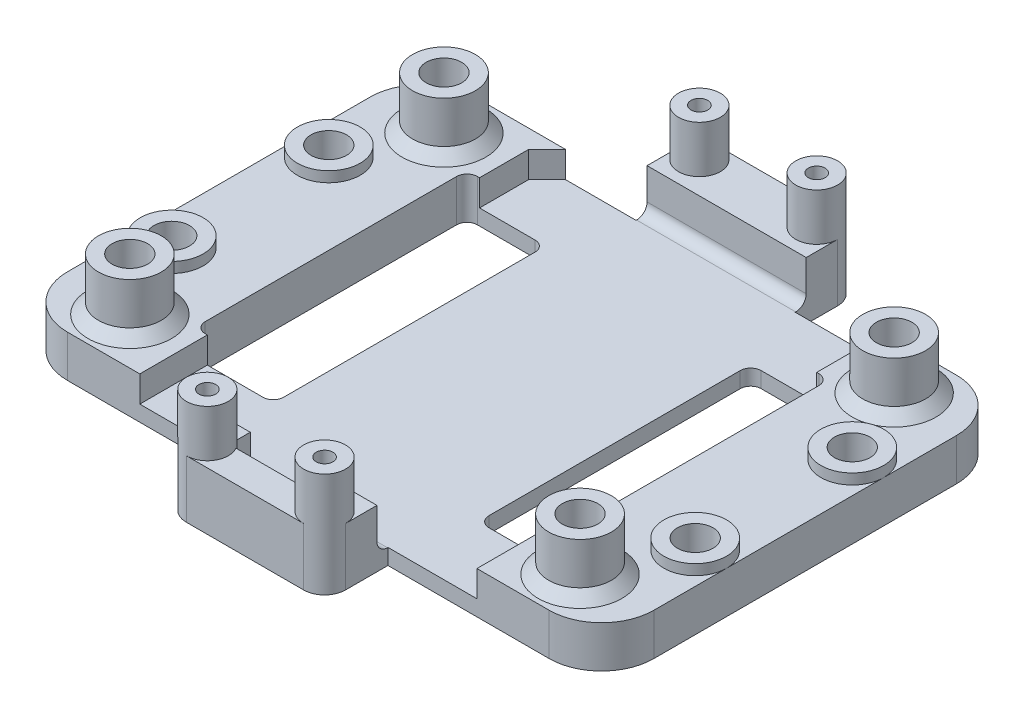
SolidWorks part; units mm, degrees
ref_plane "Front Plane" through (0, 0, 0) normal (0, 0, 1) x (1, 0, 0)
ref_plane "Top Plane" through (0, 0, 0) normal (0, 1, 0) x (1, 0, 0)
ref_plane "Right Plane" through (0, 0, 0) normal (1, 0, 0) x (0, 0, -1)
sketch "Sketch1" plane through (0, 0, 0) normal (0, 1, 0) x (1, 0, 0)
  line L0 (-15.6, 17.4701) -> (-13.6201, 19.45)
  line L1 (-13.6201, 19.45) -> (13.6201, 19.45)
  line L2 (-15.6, 17.4701) -> (-15.6, -19.45)
  line L3 (-15.6, -19.45) -> (15.6, -19.45)
  line L4 (15.6, 17.4701) -> (15.6, -19.45)
  line L5 (-14.7188, 18.3513) -> (15.6, -19.45) construction
  line L6 (-15.6, -19.45) -> (14.7188, 18.3513) construction
  line L7 (-13.6201, 19.45) -> (13.6201, 19.45)
  line L8 (13.6201, 19.45) -> (15.6, 17.4701)
  point P0 (0, 0)
  dimension "D1" = 31.2
  dimension "D2" = 38.9
  dimension "D3" = 45
  dimension "D4" = 2.8
  dimension "D5" = 2.8
  dimension "D6" = 19.45
  dimension "D7" = 15.6
sketch "Sketch2" plane through (0, 0, 0) normal (0, 1, 0) x (1, 0, 0)
  line L1 (-25, 7.5) -> (25, 7.5) construction
  line L2 (-25, 7.5) -> (-25, -7.5) construction
  line L3 (-25, -7.5) -> (25, -7.5) construction
  line L4 (25, 7.5) -> (25, -7.5) construction
  line L5 (-25, 7.5) -> (25, -7.5) construction
  line L6 (-25, -7.5) -> (25, 7.5) construction
  circle A0 centre (-25, 7.5) radius 1.7
  circle A1 centre (-25, -7.5) radius 1.7
  circle A2 centre (25, -7.5) radius 1.7
  circle A3 centre (25, 7.5) radius 1.7
  circle A4 centre (-25, 7.5) radius 3
  circle A5 centre (-25, -7.5) radius 3
  circle A6 centre (25, -7.5) radius 3
  circle A7 centre (25, 7.5) radius 3
  point P0 (0, 0)
  dimension "D3" = 3.4
  dimension "D4" = 6
  dimension "D1" = 50
  dimension "D2" = 15
extrude "Boss-Extrude1" add sketch "Sketch2" along normal blind 5
sketch "Sketch3" plane through (0, 0, 0) normal (0, 1, 0) x (1, 0, 0)
  line L0 (-13.6201, 19.45) -> (13.6201, 19.45) construction
  line L1 (-28, -19.45) -> (28, -19.45)
  line L2 (-28, -19.45) -> (-28, 19.45)
  line L3 (-28, 19.45) -> (28, 19.45)
  line L4 (28, -19.45) -> (28, 19.45)
  line L5 (-28, -19.45) -> (28, 19.45) construction
  line L6 (-28, 19.45) -> (28, -19.45) construction
  circle A0 centre (-25, 7.5) radius 3 construction
  circle A1 centre (-25, 7.5) radius 1.7 construction
  circle A2 centre (-25, 7.5) radius 1.7
  circle A3 centre (25, 7.5) radius 1.7 construction
  circle A4 centre (25, -7.5) radius 1.7 construction
  circle A5 centre (-25, -7.5) radius 1.7 construction
  circle A6 centre (25, 7.5) radius 1.7
  circle A7 centre (25, -7.5) radius 1.7
  circle A8 centre (-25, -7.5) radius 1.7
  point P0 (0, 0)
extrude "Boss-Extrude2" add sketch "Sketch3" along normal blind 4
fillet "Fillet1" radius 5 4 edges at (-28, 2, -19.45) (28, 2, -19.45) (28, 2, 19.45) (-28, 2, 19.45)
extrude "Cut-Extrude2" cut sketch "Sketch1" against normal blind 2.5 from surface contours L8 L1 L0 L2 L3 L4 region at (0, 0, 0.0609) starting at face at (0, 4, -0.75)
sketch "Sketch4" plane through (0, 4, 0) normal (0, 1, 0) x (1, 0, 0)
  line L41 (-16.1, -19.95) -> (16.1, -19.95)
  line L42 (13.8272, 19.95) -> (-13.8272, 19.95)
  line L43 (16.1, -19.95) -> (16.1, 17.6772)
  line L44 (16.1, 17.6772) -> (13.8272, 19.95)
  line L45 (-16.1, 17.6772) -> (-16.1, -19.95)
  line L46 (-13.8272, 19.95) -> (-16.1, 17.6772)
  line L47 (-16.1, -19.95) -> (16.1, -19.95)
  line L48 (13.8272, 19.95) -> (-13.8272, 19.95)
  line L49 (16.1, -19.95) -> (16.1, 17.6772)
  line L50 (16.1, 17.6772) -> (13.8272, 19.95)
  line L51 (-16.1, 17.6772) -> (-16.1, -19.95)
  line L52 (-13.8272, 19.95) -> (-16.1, 17.6772)
  dimension "D1" = 0.5
extrude "Cut-Extrude3" cut sketch "Sketch4" against normal up to surface (2.5 mm away) up to face at (0, 1.5, -5.8234)
sketch "Sketch5" plane through (0, 4, 0) normal (0, 1, 0) x (1, 0, 0)
  line L1 (-21.5, 15) -> (21.5, 15) construction
  line L2 (-21.5, 15) -> (-21.5, -15) construction
  line L3 (-21.5, -15) -> (21.5, -15) construction
  line L4 (21.5, 15) -> (21.5, -15) construction
  line L5 (-21.5, 15) -> (21.5, -15) construction
  line L6 (-21.5, -15) -> (21.5, 15) construction
  circle A0 centre (-21.5, 15) radius 1.7
  circle A1 centre (21.5, 15) radius 1.7
  circle A2 centre (21.5, -15) radius 1.7
  circle A3 centre (-21.5, -15) radius 1.7
  circle A4 centre (-21.5, 15) radius 3
  circle A5 centre (21.5, 15) radius 3
  circle A6 centre (21.5, -15) radius 3
  circle A7 centre (-21.5, -15) radius 3
  point P0 (0, 0)
  dimension "D1" = 3.4
  dimension "D4" = 6
  dimension "D2" = 43
  dimension "D3" = 30
extrude "Boss-Extrude3" add sketch "Sketch5" along normal blind 5
extrude "Cut-Extrude4" cut sketch "Sketch5<2>" against normal through all contours A0 | A3 | A2 | A1
sketch "Sketch5<2>" plane through (0, 4, 0) normal (0, 1, 0) x (1, 0, 0) same geometry as "Sketch5"
sketch "Sketch6" plane through (0, 0, 0) normal (0, -1, 0) x (1, 0, 0)
  line L1 (-19.97, 12.35) -> (-18.44, 15)
  line L2 (-18.44, 15) -> (-19.97, 17.65)
  line L3 (-19.97, 17.65) -> (-23.03, 17.65)
  line L4 (-23.03, 17.65) -> (-24.56, 15)
  line L5 (-24.56, 15) -> (-23.03, 12.35)
  line L6 (-23.03, 12.35) -> (-19.97, 12.35)
  line L7 (23.03, 12.35) -> (24.56, 15)
  line L8 (24.56, 15) -> (23.03, 17.65)
  line L9 (23.03, 17.65) -> (19.97, 17.65)
  line L10 (19.97, 17.65) -> (18.44, 15)
  line L11 (18.44, 15) -> (19.97, 12.35)
  line L12 (19.97, 12.35) -> (23.03, 12.35)
  line L13 (24.56, -15) -> (23.03, -12.35)
  line L14 (23.03, -12.35) -> (19.97, -12.35)
  line L15 (19.97, -12.35) -> (18.44, -15)
  line L16 (18.44, -15) -> (19.97, -17.65)
  line L17 (19.97, -17.65) -> (23.03, -17.65)
  line L18 (23.03, -17.65) -> (24.56, -15)
  line L19 (-18.44, -15) -> (-19.97, -12.35)
  line L20 (-19.97, -12.35) -> (-23.03, -12.35)
  line L21 (-23.03, -12.35) -> (-24.56, -15)
  line L22 (-24.56, -15) -> (-23.03, -17.65)
  line L23 (-23.03, -17.65) -> (-19.97, -17.65)
  line L24 (-19.97, -17.65) -> (-18.44, -15)
  circle A0 centre (-21.5, 15) radius 2.65 construction
  circle A1 centre (21.5, 15) radius 2.65 construction
  circle A2 centre (21.5, -15) radius 2.65 construction
  circle A3 centre (-21.5, -15) radius 2.65 construction
  dimension "D1" = 5.3
extrude "Cut-Extrude5" cut sketch "Sketch6" against normal blind 2.5
chamfer "Chamfer1" distance 1 angle 45 1 edges at (-21.5, 4, 12)
chamfer "Chamfer2" distance 1 angle 45 3 edges at (21.5, 4, 12) (21.5, 4, -18) (-21.5, 4, -18)
sketch "Sketch7" plane through (0, 1.5, 0) normal (0, 1, 0) x (1, 0, 0)
  line L1 (-9.8, -13) -> (-17.3, -13)
  line L2 (-9.8, -13) -> (-9.8, 13)
  line L3 (-9.8, 13) -> (-17.3, 13)
  line L4 (-17.3, -13) -> (-17.3, 13)
  line L5 (-9.8, -13) -> (-17.3, 13) construction
  line L6 (-9.8, 13) -> (-17.3, -13) construction
  line L8 (9.8, -13) -> (17.3, -13)
  line L9 (9.8, -13) -> (9.8, 13)
  line L10 (9.8, 13) -> (17.3, 13)
  line L11 (17.3, -13) -> (17.3, 13)
  line L12 (9.8, -13) -> (17.3, 13) construction
  line L13 (9.8, 13) -> (17.3, -13) construction
  point P0 (-13.55, 0)
  point P7 (13.55, 0)
  dimension "D1" = 7.5
  dimension "D2" = 26
extrude "Cut-Extrude6" cut sketch "Sketch7" against normal through all both and the other way through all
fillet "Fillet3" radius 1 8 edges at (-17.3, 2, 13) (-9.8, 0.75, 13) (-17.3, 2, -13) (-9.8, 0.75, -13) (9.8, 0.75, 13) (17.3, 2, 13) (9.8, 0.75, -13) (17.3, 2, -13)
sketch "Sketch8" plane through (0, 0, 0) normal (0, 1, 0) x (1, 0, 0)
  line L0 (-5.6, -23.5) -> (5.6, -23.5) construction
  line L1 (-5.6, -23.5) -> (-5.6, 23.5) construction
  line L2 (-5.6, 23.5) -> (5.6, 23.5) construction
  line L3 (5.6, -23.5) -> (5.6, 23.5) construction
  line L4 (-5.6, -23.5) -> (5.6, 23.5) construction
  line L5 (-5.6, 23.5) -> (5.6, -23.5) construction
  circle A0 centre (-5.6, 23.5) radius 0.8
  circle A1 centre (5.6, 23.5) radius 0.8
  circle A2 centre (5.6, -23.5) radius 0.8
  circle A3 centre (-5.6, -23.5) radius 0.8
  circle A4 centre (-5.6, 23.5) radius 2
  circle A5 centre (5.6, 23.5) radius 2
  circle A6 centre (-5.6, -23.5) radius 2
  circle A7 centre (5.6, -23.5) radius 2
  point P0 (0, 0)
  dimension "D1" = 1.6
  dimension "D2" = 4
  dimension "D3" = 11.2
  dimension "D4" = 47
extrude "Boss-Extrude4" add sketch "Sketch8" along normal blind 10 separate body
sketch "Sketch9" plane through (0, 0, 0) normal (0, 1, 0) x (1, 0, 0)
  line L0 (-5.6, -25.5) -> (5.6, -25.5)
  line L1 (-7.6, -23.5) -> (-7.6, 23.5)
  line L2 (-5.6, 25.5) -> (5.6, 25.5)
  line L3 (7.6, -23.5) -> (7.6, 23.5)
  line L4 (-6.852, -25.0597) -> (6.852, 25.0597) construction
  line L5 (-6.8645, 21.9504) -> (7.522, -24.0531) construction
  arc A0 (5.6, -25.5) -> (7.6, -23.5) centre (5.6, -23.5) ccw
  arc A1 (-7.6, -23.5) -> (-5.6, -25.5) centre (-5.6, -23.5) ccw
  arc A2 (7.6, 23.5) -> (5.6, 25.5) centre (5.6, 23.5) ccw
  arc A3 (-5.6, 25.5) -> (-7.6, 23.5) centre (-5.6, 23.5) ccw
  circle A4 centre (-5.6, 23.5) radius 2 construction
  circle A5 centre (5.6, 23.5) radius 2 construction
  circle A6 centre (-5.6, -23.5) radius 2 construction
  circle A7 centre (5.6, -23.5) radius 2 construction
  point P0 (0, 0)
  point P18 (0, 0)
extrude "Boss-Extrude5" add sketch "Sketch9" along normal up to surface (1.5 mm away) up to face at (0, 1.5, -1.9641)
sketch "Sketch10" plane through (0, 1.5, 0) normal (0, 1, 0) x (1, 0, 0)
  line L0 (7.6, 23.5) -> (7.6, 19.45) construction
  line L1 (-7.6, 19.45) -> (-7.6, 23.5) construction
  line L2 (-5.6, 25.5) -> (5.6, 25.5) construction
  line L3 (7.6, 23.5) -> (7.6, 20.5)
  line L4 (-7.6, 20.5) -> (-7.6, 23.5)
  line L5 (-5.6, 25.5) -> (5.6, 25.5)
  line L6 (-7.6, 20.5) -> (7.6, 20.5)
  line L7 (-1000.2677, 0) -> (48999.7323, 0) construction
  line L9 (-5.6, -25.5) -> (5.6, -25.5)
  line L10 (-7.6, -20.5) -> (-7.6, -23.5)
  line L11 (7.6, -23.5) -> (7.6, -20.5)
  line L12 (-7.6, -20.5) -> (-4.5, -20.5)
  line L13 (-4.5, -22.5) -> (4.5, -22.5)
  line L14 (-4.5, -22.5) -> (-4.5, -20.5)
  line L16 (4.5, -22.5) -> (4.5, -20.5)
  line L17 (-4.5, -22.5) -> (4.5, -20.5) construction
  line L18 (-4.5, -20.5) -> (4.5, -22.5) construction
  line L19 (4.5, -20.5) -> (7.6, -20.5)
  circle A0 centre (-5.6, 23.5) radius 2 construction
  circle A1 centre (5.6, 23.5) radius 2 construction
  arc A2 (-5.6, 25.5) -> (-7.6, 23.5) centre (-5.6, 23.5) ccw
  arc A3 (7.6, 23.5) -> (5.6, 25.5) centre (5.6, 23.5) ccw
  arc A4 (7.6, -23.5) -> (5.6, -25.5) centre (5.6, -23.5) cw
  arc A5 (-5.6, -25.5) -> (-7.6, -23.5) centre (-5.6, -23.5) cw
  point P23 (0, -21.5)
  dimension "D1" = 5
  dimension "D2" = 2
  dimension "D3" = 9
extrude "Boss-Extrude7" add sketch "Sketch10" along normal blind 4
fillet "Fillet4" radius 1 4 edges at (0, 1.5, -20.5) (0, 1.5, 22.5) (-6.05, 1.5, 20.5) (6.05, 1.5, 20.5)
